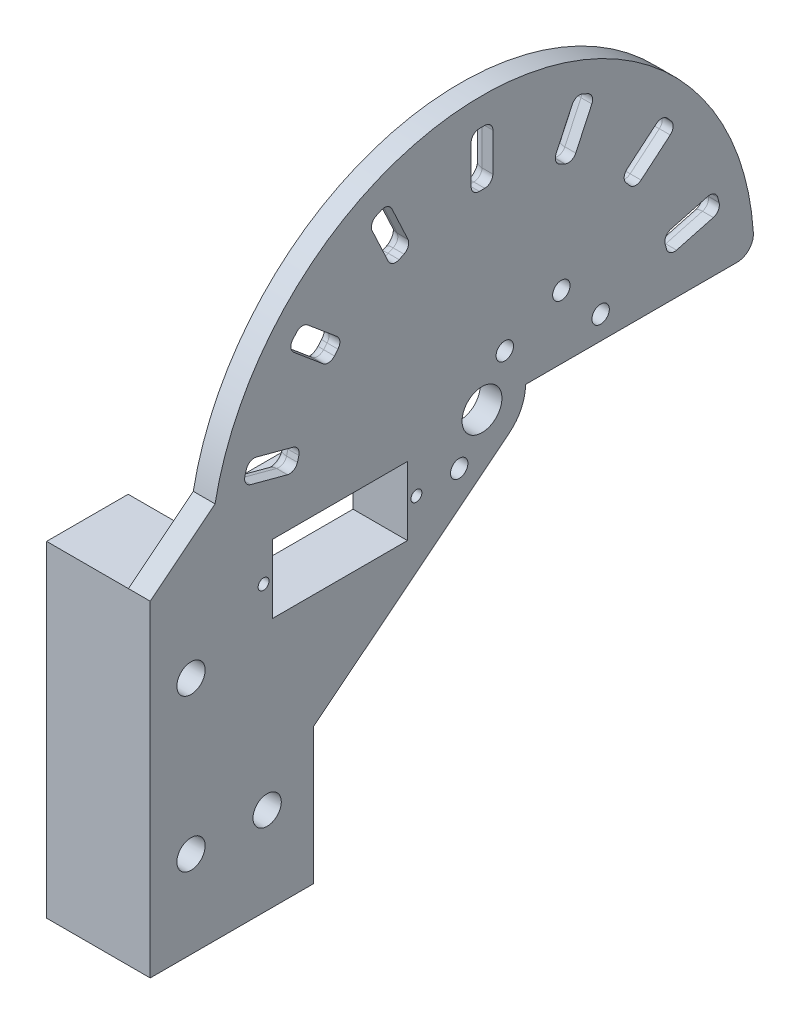
SolidWorks part; units mm, degrees
note: The reader was unsure of these and kept them because the rebuilt part matched: shared geometry of "Sketch1<3>", "Sketch1<5>", "Sketch3<3>", "Sketch4<3>".
ref_plane "Front" through (0, 0, 0) normal (0, 0, 1) x (1, 0, 0)
ref_plane "Top" through (0, 0, 0) normal (0, 1, 0) x (1, 0, 0)
ref_plane "Right" through (0, 0, 0) normal (1, 0, 0) x (0, 0, -1)
sketch "Sketch1" plane through (0, 0, 0) normal (1, 0, 0) x (0, 0, -1)
  line L0 (-38.5096, 58.6031) -> (-13.7096, 58.6031)
  line L2 (-7.7096, 43.0031) -> (-7.7096, 61.6031)
  line L3 (-7.7096, 61.6031) -> (-44.5096, 61.6031)
  line L4 (-44.5096, 61.6031) -> (-44.5096, 43.0031)
  line L13 (-38.5096, 58.6031) -> (-38.5096, 46.0031)
  line L14 (-14.3096, 47.3031) -> (-14.3096, 57.3031)
  line L15 (-15.6096, 58.6031) -> (-36.6096, 58.6031)
  line L16 (-37.9096, 57.3031) -> (-37.9096, 47.3031)
  line L17 (-36.6096, 46.0031) -> (-15.6096, 46.0031)
  line L18 (-14.3096, 47.3031) -> (-14.3096, 57.3031) construction
  line L19 (-15.6096, 58.6031) -> (-36.6096, 58.6031) construction
  line L20 (-37.9096, 57.3031) -> (-37.9096, 47.3031) construction
  line L21 (-36.6096, 46.0031) -> (-15.6096, 46.0031) construction
  line L23 (-13.7096, 46.0031) -> (-13.7096, 58.6031)
  line L24 (-38.5096, 46.0031) -> (-13.7096, 46.0031)
  line L25 (4.9928, 53.7492) -> (-31, 25)
  line L26 (-7.7096, 43.0031) -> (-44.5096, 43.0031)
  line L27 (-1.0492, 67.9309) -> (-61, 60)
  line L28 (-61, 60) -> (-61, 0)
  line L29 (-61, 0) -> (-31, 0)
  line L30 (-31, 0) -> (-31, 25)
  line L31 (-65, -6) -> (-65, 60) construction
  line L32 (65, -6) -> (-65, -6) construction
  line L33 (65, 60) -> (-65, 60) construction
  line L38 (-13.7096, 46.0031) -> (-13.7096, 55.2447)
  line L42 (-14.0897, 58.456) -> (-4.191, 52.741) construction
  line L43 (-14.0897, 58.456) -> (-4.191, 52.741) construction
  arc A2 (-1.0492, 67.9309) -> (4.9928, 53.7492) centre (0, 60) cw
  circle A13 centre (0, 60) radius 3.6655
  arc A14 (-15.6096, 46.0031) -> (-14.3096, 47.3031) centre (-15.6096, 47.3031) ccw
  arc A15 (-14.3096, 57.3031) -> (-15.6096, 58.6031) centre (-15.6096, 57.3031) ccw
  arc A16 (-36.6096, 58.6031) -> (-37.9096, 57.3031) centre (-36.6096, 57.3031) ccw
  arc A17 (-37.9096, 47.3031) -> (-36.6096, 46.0031) centre (-36.6096, 47.3031) ccw
  arc A18 (-15.6096, 46.0031) -> (-14.3096, 47.3031) centre (-15.6096, 47.3031) ccw construction
  arc A19 (-14.3096, 57.3031) -> (-15.6096, 58.6031) centre (-15.6096, 57.3031) ccw construction
  arc A20 (-36.6096, 58.6031) -> (-37.9096, 57.3031) centre (-36.6096, 57.3031) ccw construction
  arc A21 (-37.9096, 47.3031) -> (-36.6096, 46.0031) centre (-36.6096, 47.3031) ccw construction
  circle A22 centre (0, 60) radius 3.6655
  circle A34 centre (-4.191, 52.741) radius 1.6
  dimension "D2" = 8
  dimension "D9" = 3.2
  dimension "D3" = 6
  dimension "D4" = 6
  dimension "D5" = 3
  dimension "D7" = 4
  dimension "D8" = 6
  dimension "D10" = 25
  dimension "D11" = 3
  dimension "D12" = 30
  dimension "D13" = 0.6
  dimension "D14" = 0.6
  dimension "D1" = 0.3
  dimension "D6" = 0.3
extrude "Boss-Extrude1" add sketch "Sketch1" along normal blind 10 from surface
extrude "Boss-Extrude2" add sketch "Sketch1<3>" against normal blind 4 from surface at -11.95
sketch "Sketch1<3>" plane through (0, 0, 0) normal (1, 0, 0) x (0, 0, -1) same geometry as "Sketch1"
extrude "Boss-Extrude3" add sketch "Sketch1<5>" against normal blind 4 from surface at -11.95 starting at face at (-11.95, 52.3031, 26.1096)
sketch "Sketch1<5>" plane through (0, 0, 0) normal (1, 0, 0) x (0, 0, -1) same geometry as "Sketch1"
sketch "Sketch2" plane through (-15.95, 0, 0) normal (-1, 0, 0) x (0, 0, 1)
  line L0 (31, 25) -> (31, 30)
  line L1 (31, 30) -> (46, 30)
  line L2 (46, 30) -> (46, 60)
  line L3 (46, 60) -> (61, 60)
  line L4 (61, 60) -> (61, 0) construction
  line L5 (61, 60) -> (61, 0)
  line L6 (61, 0) -> (31, 0)
  line L7 (61, 0) -> (31, 0) construction
  line L8 (31, 0) -> (31, 25)
  line L9 (-65, 60) -> (65, 60) construction
  line L10 (31, 0) -> (31, 25) construction
  dimension "D1" = 15
  dimension "D2" = 30
extrude "Boss-Extrude4" add sketch "Sketch2" along normal up to surface (15.05 mm away)
sketch "Sketch3" plane through (0, 0, 0) normal (0, -1, 0) x (1, 0, 0)
  line L0 (-21.475, 53.5) -> (-21.475, 38.5) construction
  line L1 (-11.95, 46) -> (-31, 46) construction
  line L4 (-11.95, 31) -> (-11.95, 61)
  line L5 (-11.95, 61) -> (-31, 61)
  line L6 (-31, 61) -> (-31, 31)
  line L7 (-31, 31) -> (-11.95, 31)
  line L8 (-11.95, 31) -> (-11.95, 61)
  line L9 (-11.95, 61) -> (-31, 61)
  line L10 (-31, 61) -> (-31, 31)
  line L11 (-31, 31) -> (-11.95, 31)
  circle A0 centre (-21.475, 53.5) radius 2.6
  circle A1 centre (-21.475, 38.5) radius 2.6
  circle A2 centre (-21.475, 53.5) radius 1.6
  circle A3 centre (-21.475, 38.5) radius 1.6
  point P11 (-21.475, 46)
  point P12 (-21.475, 46)
  dimension "D2" = 5.2
  dimension "D3" = 5.2
  dimension "D5" = 3.2
  dimension "D6" = 3.2
  dimension "D4" = 15
extrude "Cut-Extrude1" cut sketch "Sketch3" against normal blind 3.9 draft 1.5 contours A0 | A1
extrude "Cut-Extrude2" cut sketch "Sketch3<3>" against normal blind 10 contours A2 | A3
sketch "Sketch3<3>" plane through (0, 0, 0) normal (0, -1, 0) x (1, 0, 0) same geometry as "Sketch3"
sketch "Sketch4" plane through (-11.95, 0, 0) normal (1, 0, 0) x (0, 0, -1)
  line L0 (-61, 0) -> (-31, 0) construction
  line L1 (-61, 0) -> (-31, 0) construction
  line L2 (-46, 60) -> (-61, 60) construction
  line L3 (-46, 60) -> (-61, 60) construction
  line L4 (-53.5, 60) -> (-53.5, 0) construction
  line L5 (-53.5, 16) -> (-39.5, 16) construction
  circle A0 centre (-39.5, 16) radius 2.6
  circle A2 centre (-53.5, 44) radius 2.6
  circle A3 centre (-53.5, 16) radius 2.6
  circle A4 centre (-53.5, 44) radius 1.6
  circle A5 centre (-53.5, 16) radius 1.6
  circle A6 centre (-39.5, 16) radius 1.6
  dimension "D4" = 5.2
  dimension "D5" = 5.2
  dimension "D6" = 5.2
  dimension "D7" = 3.2
  dimension "D8" = 3.2
  dimension "D9" = 3.2
  dimension "D1" = 16
  dimension "D2" = 16
  dimension "D3" = 14
extrude "Cut-Extrude3" cut sketch "Sketch4" against normal through all contours A4 | A5 | A6
extrude "Cut-Extrude4" cut sketch "Sketch4<3>" against normal blind 3.9 draft 1.5 contours A2 | A3 | A0
sketch "Sketch4<3>" plane through (-11.95, 0, 0) normal (1, 0, 0) x (0, 0, -1) same geometry as "Sketch4"
sketch "Sketch5" plane through (-11.95, 0, 0) normal (1, 0, 0) x (0, 0, -1)
  line L0 (-61, 60) -> (-41, 76)
  line L1 (-41, 76) -> (26, 76)
  line L2 (26, 76) -> (26, 60)
  line L3 (26, 60) -> (8, 60)
  line L5 (-31, 0) -> (-31, 25)
  line L6 (-31, 25) -> (4.9928, 53.7492)
  line L7 (-1.0492, 67.9309) -> (-61, 60)
  line L8 (-61, 60) -> (-61, 0)
  line L9 (-61, 0) -> (-31, 0)
  line L10 (-31, 0) -> (-31, 25)
  line L11 (-31, 25) -> (4.9928, 53.7492)
  line L12 (-1.0492, 67.9309) -> (-61, 60)
  line L13 (-61, 60) -> (-61, 0)
  line L14 (-61, 0) -> (-31, 0)
  arc A1 (4.9928, 53.7492) -> (-1.0492, 67.9309) centre (0, 60) ccw
  arc A2 (4.9928, 53.7492) -> (-1.0492, 67.9309) centre (0, 60) ccw
  arc M16 (4.9928, 53.7492) -> (-1.0492, 67.9309) centre (0, 60) ccw
  line M17 (-1.0492, 67.9309) -> (-61, 60)
  dimension "D2" = 16
  dimension "D3" = 18
  dimension "D4" = 16
  dimension "D5" = 20
  dimension "D1" = 0
extrude "Boss-Extrude5" add sketch "Sketch5" against normal up to surface (4 mm away) contours L3 L2 L1 L0 M17 M16 up to face at (-15.95, 63.6655, 0)
sketch "Sketch6" plane through (-15.95, 0, 0) normal (-1, 0, 0) x (0, 0, 1)
  line L14 (46, 60) -> (61, 60)
  line L15 (61, 60) -> (41, 76)
  line L16 (41, 76) -> (-26, 76)
  line L17 (-26, 76) -> (-26, 60)
  line L18 (-26, 60) -> (-8, 60)
  line L19 (-4.9928, 53.7492) -> (7.7096, 43.6032)
  line L20 (7.7096, 43.6032) -> (7.7096, 61.6031)
  line L21 (7.7096, 61.6031) -> (44.5096, 61.6031)
  line L22 (44.5096, 61.6031) -> (44.5096, 43.0031)
  line L23 (44.5096, 43.0031) -> (8.461, 43.0031)
  line L24 (8.461, 43.0031) -> (31, 25)
  line L25 (31, 25) -> (31, 30)
  line L26 (31, 30) -> (46, 30)
  line L27 (46, 30) -> (46, 60)
  line L28 (46, 60) -> (61, 60)
  line L29 (61, 60) -> (41, 76)
  line L30 (41, 76) -> (-26, 76)
  line L31 (-26, 76) -> (-26, 60)
  line L32 (-26, 60) -> (-8, 60)
  line L33 (-4.9928, 53.7492) -> (7.7096, 43.6032)
  line L34 (7.7096, 43.6032) -> (7.7096, 61.6031)
  line L35 (7.7096, 61.6031) -> (44.5096, 61.6031)
  line L36 (44.5096, 61.6031) -> (44.5096, 43.0031)
  line L37 (44.5096, 43.0031) -> (8.461, 43.0031)
  line L38 (8.461, 43.0031) -> (31, 25)
  line L39 (31, 25) -> (31, 30)
  line L40 (31, 30) -> (46, 30)
  line L41 (46, 30) -> (46, 60)
  arc A1 (-8, 60) -> (-4.9928, 53.7492) centre (0, 60) ccw
  arc A2 (-8, 60) -> (-4.9928, 53.7492) centre (0, 60) ccw
  circle A4 centre (-14.5886, 71.704) radius 1.6
  circle A5 centre (-21.8114, 64.296) radius 1.6
  dimension "D1" = 0
extrude "Cut-Extrude5" cut sketch "Sketch6" against normal through all contours A4 | A5
sketch "Sketch7" plane through (-15.95, 0, 0) normal (-1, 0, 0) x (0, 0, 1)
  line L0 (0, 60) -> (3.1744, 61.8327) construction
  line L1 (0, 60) -> (4.191, 52.741) construction
  circle A0 centre (0, 60) radius 3.6655 construction
  circle A1 centre (0, 60) radius 3.6655
  circle A2 centre (4.191, 52.741) radius 1.6 construction
  circle A3 centre (4.191, 52.741) radius 1.6
  circle A4 centre (-4.191, 67.259) radius 1.6
extrude "Cut-Extrude6" cut sketch "Sketch7" against normal through all contours A4
sketch "Sketch8" plane through (-21.95, 0, 0) normal (-1, 0, 0) x (0, 0, 1)
  line L0 (12.5596, 52.3031) -> (50012.5596, 52.3031) construction
  line L5 (7.7096, 43.6032) -> (8.461, 43.0031)
  line L6 (8.461, 43.0031) -> (44.5096, 43.0031)
  line L7 (44.5096, 43.0031) -> (44.5096, 61.6031)
  line L8 (44.5096, 61.6031) -> (7.7096, 61.6031)
  line L9 (7.7096, 61.6031) -> (7.7096, 43.6032)
  line L10 (7.7096, 43.6032) -> (8.461, 43.0031)
  line L11 (8.461, 43.0031) -> (44.5096, 43.0031)
  line L12 (44.5096, 43.0031) -> (44.5096, 61.6031)
  line L13 (44.5096, 61.6031) -> (7.7096, 61.6031)
  line L14 (7.7096, 61.6031) -> (7.7096, 43.6032)
  arc A0 (37.6096, 52.3031) -> (41.4236, 51.2586) centre (39.6596, 52.3031) ccw construction
  arc A1 (41.4236, 53.3476) -> (37.6096, 52.3031) centre (39.6596, 52.3031) ccw construction
  arc A2 (10.7957, 51.2586) -> (14.6096, 52.3031) centre (12.5596, 52.3031) ccw construction
  arc A3 (14.6096, 52.3031) -> (10.7957, 53.3476) centre (12.5596, 52.3031) ccw construction
  arc A4 (37.6096, 52.3031) -> (41.4236, 51.2586) centre (39.6596, 52.3031) ccw
  arc A5 (41.4236, 53.3476) -> (37.6096, 52.3031) centre (39.6596, 52.3031) ccw
  arc A6 (10.7957, 51.2586) -> (14.6096, 52.3031) centre (12.5596, 52.3031) ccw
  arc A7 (14.6096, 52.3031) -> (10.7957, 53.3476) centre (12.5596, 52.3031) ccw
  circle A8 centre (12.0596, 52.3031) radius 1
  circle A9 centre (40.1596, 52.3031) radius 1
  dimension "D2" = 2
  dimension "D3" = 2
  dimension "D4" = 0.5
  dimension "D5" = 0.5
  dimension "D1" = 0
extrude "Cut-Extrude7" cut sketch "Sketch8" against normal through all contours A8 | A9
sketch "Detent Positions Sketch" plane through (-15.95, 0, 0) normal (-1, 0, 0) x (0, 0, 1)
  line L0 (-53.1259, 74.235) -> (0, 60) construction
  line L1 (0, 60) -> (53.1259, 74.235) construction
  line L2 (-53.1259, 74.235) -> (0, 60) construction
  line L3 (0, 60) -> (53.1259, 74.235) construction
  line L4 (0, 60) -> (42.1324, 95.3533) construction
  line L5 (0, 60) -> (23.244, 109.8469) construction
  line L6 (0, 60) -> (0, 115) construction
  line L7 (0, 60) -> (-23.244, 109.8469) construction
  line L8 (0, 60) -> (-42.1324, 95.3533) construction
  line L9 (0, 60) -> (-53.1259, 74.235) construction
  circle A0 centre (0, 60) radius 3.6655 construction
  circle A1 centre (0, 60) radius 3.6655
  arc A2 (24.1481, 66.4705) -> (-24.1481, 66.4705) centre (0, 60) ccw construction
  arc A3 (24.1481, 66.4705) -> (-24.1481, 66.4705) centre (0, 60) ccw construction
  point P10 (24.1481, 66.4705)
  point P19 (0, 60)
  dimension "D1" = 150
  dimension "D2" = 7
sketch "Sketch10" plane through (-15.95, 0, 0) normal (-1, 0, 0) x (0, 0, 1)
  line L0 (-26, 76) -> (41, 76) construction
  line L1 (-26, 60) -> (-26, 76) construction
  line L2 (-26, 76) -> (41, 76)
  line L3 (-26, 60) -> (-26, 76)
  line L4 (-26, 60) -> (-46.9042, 60)
  line L5 (41, 76) -> (61, 60) construction
  line L6 (41, 76) -> (61, 60)
  circle A0 centre (0, 60) radius 3.6655 construction
  circle A1 centre (0, 60) radius 3.6655
  arc A2 (-49.898, 63.1915) -> (49.0826, 69.5339) centre (0, 60) cw
  arc A3 (-46.9042, 60) -> (-49.898, 63.1915) centre (-46.9042, 63) cw
  line M8 (-26, 76) -> (-26, 60)
  dimension "D1" = 50
  dimension "D2" = 3
extrude "Boss-Extrude6" add sketch "Sketch10" against normal up to surface (4 mm away) contours A2 L4 L2 M8
sketch "Detent Cutouts" plane through (-15.95, 0, 0) normal (-1, 0, 0) x (0, 0, 1)
  line L0 (0, 60) -> (53.1259, 74.235) construction
  line L1 (0, 60) -> (53.1259, 74.235) construction
  line L2 (35.7705, 67.5141) -> (42.532, 69.3259)
  line L3 (33.9334, 68.5748) -> (33.6745, 69.5407)
  line L4 (43.5926, 71.163) -> (43.3338, 72.1289)
  line L5 (34.7352, 71.3778) -> (41.4967, 73.1896)
  line L6 (34.3216, 67.1259) -> (42.9456, 73.5778) construction
  line L7 (43.9809, 69.7141) -> (33.2863, 70.9896) construction
  line L32 (0, 60) -> (33.9334, 68.5748) construction
  line L34 (-34.7352, 71.3778) -> (-41.4967, 73.1896) [skipped]
  line L35 (-43.3338, 72.1289) -> (-43.5926, 71.163) [skipped]
  line L36 (-35.7705, 67.5141) -> (-42.532, 69.3259) [skipped]
  line L37 (-33.6745, 69.5407) -> (-33.9334, 68.5748) [skipped]
  line L38 (-26.6723, 84.9915) -> (-32.0346, 89.4911) [skipped]
  line L39 (-34.1479, 89.3062) -> (-34.7907, 88.5401) [skipped]
  line L40 (-29.2435, 81.9274) -> (-34.6058, 86.4269) [skipped]
  line L41 (-26.4874, 82.8783) -> (-27.1302, 82.1122) [skipped]
  line L42 (-13.6114, 93.9222) -> (-16.5698, 100.2664) [skipped]
  line L43 (-18.5632, 100.9919) -> (-19.4695, 100.5693) [skipped]
  line L44 (-17.2367, 92.2318) -> (-20.195, 98.5759) [skipped]
  line L45 (-14.337, 91.9288) -> (-15.2433, 91.5062) [skipped]
  line L46 (2, 96.4964) -> (2, 103.4964) [skipped]
  line L47 (0.5, 104.9964) -> (-0.5, 104.9964) [skipped]
  line L48 (-2, 96.4964) -> (-2, 103.4964) [skipped]
  line L49 (0.5, 94.9964) -> (-0.5, 94.9964) [skipped]
  line L50 (17.2367, 92.2318) -> (20.195, 98.5759) [skipped]
  line L51 (19.4695, 100.5693) -> (18.5632, 100.9919) [skipped]
  line L52 (13.6114, 93.9222) -> (16.5698, 100.2664) [skipped]
  line L53 (15.2433, 91.5062) -> (14.337, 91.9288) [skipped]
  line L55 (26.6723, 84.9915) -> (32.0346, 89.4911) [skipped]
  line L56 (34.7907, 88.5401) -> (34.1479, 89.3062) [skipped]
  line L57 (29.2435, 81.9274) -> (34.6058, 86.4269) [skipped]
  line L58 (27.1302, 82.1122) -> (26.4874, 82.8783) [skipped]
  line L59 (26.6723, 84.9915) -> (32.0346, 89.4911)
  line L60 (34.7907, 88.5401) -> (34.1479, 89.3062)
  line L61 (29.2435, 81.9274) -> (34.6058, 86.4269)
  line L62 (27.1302, 82.1122) -> (26.4874, 82.8783)
  line L63 (13.6114, 93.9222) -> (16.5698, 100.2664)
  line L64 (19.4695, 100.5693) -> (18.5632, 100.9919)
  line L65 (17.2367, 92.2318) -> (20.195, 98.5759)
  line L66 (15.2433, 91.5062) -> (14.337, 91.9288)
  line L67 (-2, 96.4964) -> (-2, 103.4964)
  line L68 (0.5, 104.9964) -> (-0.5, 104.9964)
  line L69 (2, 96.4964) -> (2, 103.4964)
  line L70 (0.5, 94.9964) -> (-0.5, 94.9964)
  line L71 (-17.2367, 92.2318) -> (-20.195, 98.5759)
  line L72 (-18.5632, 100.9919) -> (-19.4695, 100.5693)
  line L73 (-13.6114, 93.9222) -> (-16.5698, 100.2664)
  line L74 (-14.337, 91.9288) -> (-15.2433, 91.5062)
  line L75 (-29.2435, 81.9274) -> (-34.6058, 86.4269)
  line L76 (-34.1479, 89.3062) -> (-34.7907, 88.5401)
  line L77 (-26.6723, 84.9915) -> (-32.0346, 89.4911)
  line L78 (-26.4874, 82.8783) -> (-27.1302, 82.1122)
  line L79 (-35.7705, 67.5141) -> (-42.532, 69.3259)
  line L80 (-43.3338, 72.1289) -> (-43.5926, 71.163)
  line L81 (-34.7352, 71.3778) -> (-41.4967, 73.1896)
  line L82 (-33.6745, 69.5407) -> (-33.9334, 68.5748)
  line L83 (0, 60) -> (33.9334, 68.5748) construction
  line L84 (-53.1259, 74.235) -> (0, 60) construction
  arc A0 (41.4967, 73.1896) -> (43.3338, 72.1289) centre (41.8849, 71.7407) cw
  arc A1 (43.5926, 71.163) -> (42.532, 69.3259) centre (42.1437, 70.7747) cw
  arc A2 (35.7705, 67.5141) -> (33.9334, 68.5748) centre (35.3823, 68.963) cw
  arc A3 (33.6745, 69.5407) -> (34.7352, 71.3778) centre (35.1234, 69.9289) cw
  arc A28 (-43.3338, 72.1289) -> (-41.4967, 73.1896) centre (-41.8849, 71.7407) cw [skipped]
  arc A29 (-42.532, 69.3259) -> (-43.5926, 71.163) centre (-42.1437, 70.7747) cw [skipped]
  arc A30 (-33.9334, 68.5748) -> (-35.7705, 67.5141) centre (-35.3823, 68.963) cw [skipped]
  arc A31 (-34.7352, 71.3778) -> (-33.6745, 69.5407) centre (-35.1234, 69.9289) cw [skipped]
  arc A32 (-34.1479, 89.3062) -> (-32.0346, 89.4911) centre (-32.9988, 88.342) cw [skipped]
  arc A33 (-34.6058, 86.4269) -> (-34.7907, 88.5401) centre (-33.6416, 87.5759) cw [skipped]
  arc A34 (-27.1302, 82.1122) -> (-29.2435, 81.9274) centre (-28.2793, 83.0764) cw [skipped]
  arc A35 (-26.6723, 84.9915) -> (-26.4874, 82.8783) centre (-27.6365, 83.8425) cw [skipped]
  arc A36 (-18.5632, 100.9919) -> (-16.5698, 100.2664) centre (-17.9292, 99.6325) cw [skipped]
  arc A37 (-20.195, 98.5759) -> (-19.4695, 100.5693) centre (-18.8355, 99.2098) cw [skipped]
  arc A38 (-15.2433, 91.5062) -> (-17.2367, 92.2318) centre (-15.8772, 92.8657) cw [skipped]
  arc A39 (-13.6114, 93.9222) -> (-14.337, 91.9288) centre (-14.9709, 93.2883) cw [skipped]
  arc A40 (0.5, 104.9964) -> (2, 103.4964) centre (0.5, 103.4964) cw [skipped]
  arc A41 (-2, 103.4964) -> (-0.5, 104.9964) centre (-0.5, 103.4964) cw [skipped]
  arc A42 (-0.5, 94.9964) -> (-2, 96.4964) centre (-0.5, 96.4964) cw [skipped]
  arc A43 (2, 96.4964) -> (0.5, 94.9964) centre (0.5, 96.4964) cw [skipped]
  arc A44 (19.4695, 100.5693) -> (20.195, 98.5759) centre (18.8355, 99.2098) cw [skipped]
  arc A45 (16.5698, 100.2664) -> (18.5632, 100.9919) centre (17.9292, 99.6325) cw [skipped]
  arc A46 (14.337, 91.9288) -> (13.6114, 93.9222) centre (14.9709, 93.2883) cw [skipped]
  arc A47 (17.2367, 92.2318) -> (15.2433, 91.5062) centre (15.8772, 92.8657) cw [skipped]
  arc A48 (32.0346, 89.4911) -> (34.1479, 89.3062) centre (32.9988, 88.342) cw [skipped]
  arc A49 (34.7907, 88.5401) -> (34.6058, 86.4269) centre (33.6416, 87.5759) cw [skipped]
  arc A50 (29.2435, 81.9274) -> (27.1302, 82.1122) centre (28.2793, 83.0764) cw [skipped]
  arc A51 (26.4874, 82.8783) -> (26.6723, 84.9915) centre (27.6365, 83.8425) cw [skipped]
  arc A52 (32.0346, 89.4911) -> (34.1479, 89.3062) centre (32.9988, 88.342) cw
  arc A53 (34.7907, 88.5401) -> (34.6058, 86.4269) centre (33.6416, 87.5759) cw
  arc A54 (29.2435, 81.9274) -> (27.1302, 82.1122) centre (28.2793, 83.0764) cw
  arc A55 (26.4874, 82.8783) -> (26.6723, 84.9915) centre (27.6365, 83.8425) cw
  arc A56 (16.5698, 100.2664) -> (18.5632, 100.9919) centre (17.9292, 99.6325) cw
  arc A57 (19.4695, 100.5693) -> (20.195, 98.5759) centre (18.8355, 99.2098) cw
  arc A58 (17.2367, 92.2318) -> (15.2433, 91.5062) centre (15.8772, 92.8657) cw
  arc A59 (14.337, 91.9288) -> (13.6114, 93.9222) centre (14.9709, 93.2883) cw
  arc A60 (-2, 103.4964) -> (-0.5, 104.9964) centre (-0.5, 103.4964) cw
  arc A61 (0.5, 104.9964) -> (2, 103.4964) centre (0.5, 103.4964) cw
  arc A62 (2, 96.4964) -> (0.5, 94.9964) centre (0.5, 96.4964) cw
  arc A63 (-0.5, 94.9964) -> (-2, 96.4964) centre (-0.5, 96.4964) cw
  arc A64 (-20.195, 98.5759) -> (-19.4695, 100.5693) centre (-18.8355, 99.2098) cw
  arc A65 (-18.5632, 100.9919) -> (-16.5698, 100.2664) centre (-17.9292, 99.6325) cw
  arc A66 (-13.6114, 93.9222) -> (-14.337, 91.9288) centre (-14.9709, 93.2883) cw
  arc A67 (-15.2433, 91.5062) -> (-17.2367, 92.2318) centre (-15.8772, 92.8657) cw
  arc A68 (-34.6058, 86.4269) -> (-34.7907, 88.5401) centre (-33.6416, 87.5759) cw
  arc A69 (-34.1479, 89.3062) -> (-32.0346, 89.4911) centre (-32.9988, 88.342) cw
  arc A70 (-26.6723, 84.9915) -> (-26.4874, 82.8783) centre (-27.6365, 83.8425) cw
  arc A71 (-27.1302, 82.1122) -> (-29.2435, 81.9274) centre (-28.2793, 83.0764) cw
  arc A72 (-42.532, 69.3259) -> (-43.5926, 71.163) centre (-42.1437, 70.7747) cw
  arc A73 (-43.3338, 72.1289) -> (-41.4967, 73.1896) centre (-41.8849, 71.7407) cw
  arc A74 (-34.7352, 71.3778) -> (-33.6745, 69.5407) centre (-35.1234, 69.9289) cw
  arc A75 (-33.9334, 68.5748) -> (-35.7705, 67.5141) centre (-35.3823, 68.963) cw
  point P3 (38.6336, 70.3518)
  point P21 (0, 60)
  point P98 (0, 60)
  point P99 (0, 60)
  point P100 (0, 60)
  point P101 (0, 60)
  point P102 (0, 60)
  point P103 (0, 60)
  dimension "D4" = 1.5
  dimension "D1" = 4
  dimension "D2" = 10
  dimension "D8" = 35
  dimension "D5" = 7
  dimension "D7" = 7
extrude "Cut-Extrude8" cut sketch "Detent Cutouts" against normal through all
fillet "Fillet1" radius 2 56 edges at (-15.95, 73.0397, 42.6349) (-15.95, 71.6459, 43.4632) (-15.95, 70.0247, 43.4428) (-15.95, 68.42, 39.1512) (-15.95, 67.664, 34.6323) (-15.95, 69.0577, 33.804) (-15.95, 70.6789, 33.8244) (-15.95, 81.5821, 28.1485) (-15.95, 82.4953, 26.8088) (-15.95, 83.9732, 26.1422) (-15.95, 87.2413, 29.3535) (-15.95, 89.8363, 33.1295) (-15.95, 88.9231, 34.4693) (-15.95, 87.4452, 35.1359) (-15.95, 101.042, 17.4162) (-15.95, 100.7806, 19.0163) (-15.95, 99.7229, 20.2451) (-15.95, 95.4038, 18.7158) (-15.95, 91.4561, 16.3902) (-15.95, 91.7175, 14.7901) (-15.95, 92.7753, 13.5614) (-15.95, 104.5571, -1.5607) (-15.95, 104.9964, 0) (-15.95, 104.5571, 1.5607) (-15.95, 99.9964, 2) (-15.95, 95.4358, 1.5607) (-15.95, 94.9964, 0) (-15.95, 95.4358, -1.5607) (-15.95, 100.7806, -19.0163) (-15.95, 101.042, -17.4162) (-15.95, 97.0943, -15.0906) (-15.95, 92.7753, -13.5614) (-15.95, 91.7175, -14.7901) (-15.95, 91.4561, -16.3902) (-15.95, 95.4038, -18.7158) (-15.95, 83.9732, -26.1422) (-15.95, 82.4953, -26.8088) (-15.95, 81.5821, -28.1485) (-15.95, 84.1771, -31.9246) (-15.95, 87.4452, -35.1359) (-15.95, 88.9231, -34.4693) (-15.95, 89.8363, -33.1295) (-15.95, 70.6789, -33.8244) (-15.95, 69.0577, -33.804) (-15.95, 67.664, -34.6323) (-15.95, 68.42, -39.1512) (-15.95, 70.0247, -43.4428) (-15.95, 71.6459, -43.4632) (-15.95, 73.0397, -42.6349) (-15.95, 72.2837, 38.1159) (-15.95, 84.1771, 31.9246) (-15.95, 97.0943, 15.0906) (-15.95, 99.9964, -2) (-15.95, 99.7229, -20.2451) (-15.95, 87.2413, -29.3535) (-15.95, 72.2837, -38.1159)
equation "\"D3@Sketch3\"=\"D2@Sketch3\""
equation "\"D6@Sketch3\"=\"D5@Sketch3\""
equation "\"D5@Sketch4\"=\"D4@Sketch4\""
equation "\"D6@Sketch4\"=\"D4@Sketch4\""
